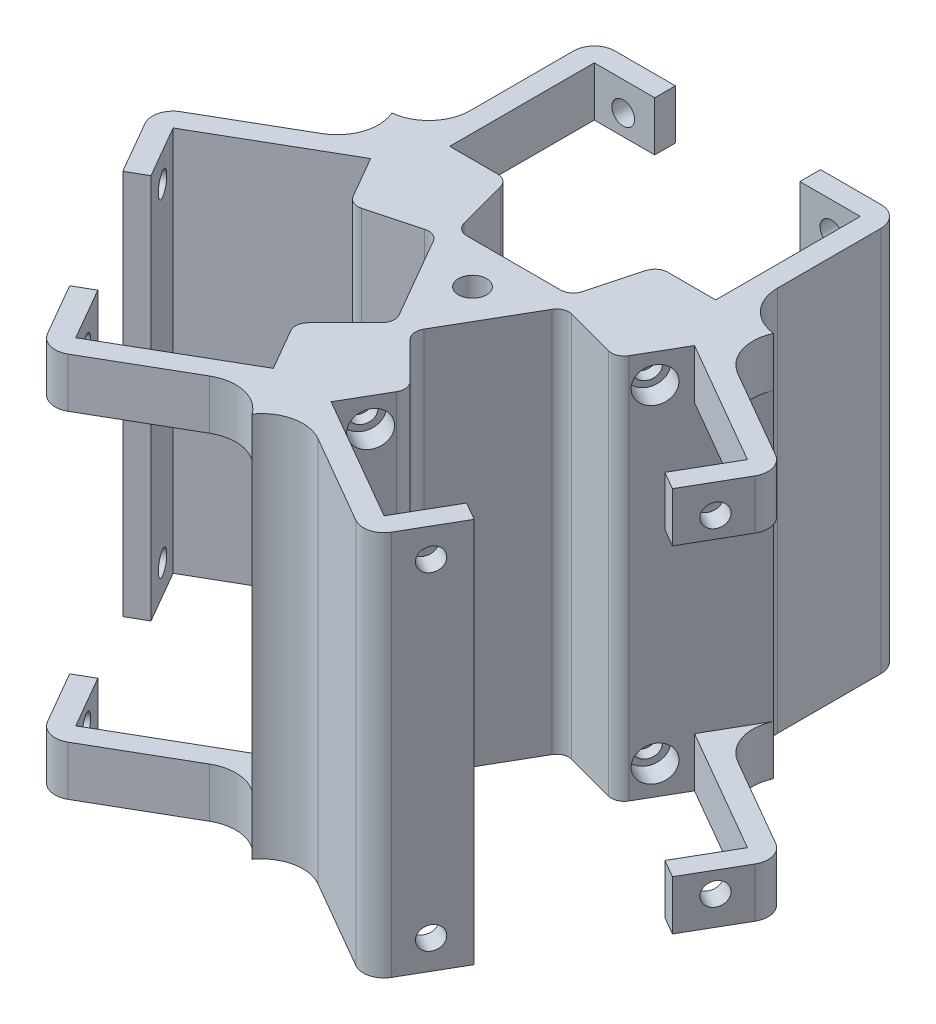
SolidWorks part; units mm, degrees
material "ABS"
ref_plane "Alzado" through (0, 0, 0) normal (0, 0, 1) x (1, 0, 0)
ref_plane "Planta" through (0, 0, 0) normal (0, 1, 0) x (1, 0, 0)
ref_plane "Vista lateral" through (0, 0, 0) normal (1, 0, 0) x (0, 0, -1)
sketch "Croquis1" plane through (0, 0, 0) normal (0, 1, 0) x (1, 0, 0)
  line L0 (0, 50.8) -> (0, -50.8) construction
  line L1 (-50.8, 0) -> (50.8, 0) construction
  line L2 (0, 0) -> (-35.921, -35.921) construction
  line L3 (0, 0) -> (35.921, -35.921) construction
  line L10 (0, -17.5) -> (-15.1554, 8.75) construction
  line L11 (-15.1554, 8.75) -> (15.1554, 8.75) construction
  line L12 (15.1554, 8.75) -> (0, -17.5) construction
  line L13 (-1.2978, -16.7522) -> (-15.1813, 7.2027) construction
  line L14 (1.2978, -16.7522) -> (15.1813, 7.2027) construction
  line L15 (-13.8835, 9.4549) -> (13.8835, 9.4549) construction
  line L16 (1.6964, -16.0645) -> (13.335, -27.7031)
  line L17 (13.335, -27.7031) -> (0, -50.8)
  line L18 (0, -50.8) -> (-13.335, -27.7031)
  line L19 (-13.335, -27.7031) -> (-1.6964, -16.0645)
  line L20 (-17.3241, 25.4) -> (-13.0641, 9.5013)
  line L21 (-43.9941, 25.4) -> (-17.3241, 25.4)
  line L22 (-30.6591, 2.3031) -> (-43.9941, 25.4)
  line L23 (-14.7604, 6.5631) -> (-30.6591, 2.3031)
  line L24 (30.6591, 2.3031) -> (14.7604, 6.5631)
  line L25 (43.9941, 25.4) -> (30.6591, 2.3031)
  line L26 (17.3241, 25.4) -> (43.9941, 25.4)
  line L27 (13.0641, 9.5013) -> (17.3241, 25.4)
  line L28 (-14.7604, 6.5631) -> (-1.6964, -16.0645)
  line L29 (1.6964, -16.0645) -> (14.7604, 6.5631)
  line L30 (-13.0641, 9.5013) -> (13.0641, 9.5013)
  line L31 (-43.9941, 25.4) -> (0, -50.8) construction
  line L32 (43.9941, 25.4) -> (0, -50.8) construction
  line L33 (-43.9941, 25.4) -> (43.9941, 25.4) construction
  circle A0 centre (0, 0) radius 50.8 construction
  circle A7 centre (0, 0) radius 17.5 construction
  circle A8 centre (-13.8835, 7.9549) radius 1.5 construction
  circle A9 centre (13.8835, 7.9549) radius 1.5 construction
  circle A10 centre (0, -16) radius 1.5 construction
  arc A11 (-15.1813, 7.2027) -> (-13.8835, 9.4549) centre (-13.8835, 7.9549) cw construction
  arc A12 (15.1813, 7.2027) -> (13.8835, 9.4549) centre (13.8835, 7.9549) ccw construction
  arc A13 (1.2978, -16.7522) -> (-1.2978, -16.7522) centre (0, -16) cw construction
  arc A14 (-15.1813, 7.2027) -> (-13.8835, 9.4549) centre (-13.8835, 7.9549) cw construction
  arc A15 (13.8835, 9.4549) -> (15.1813, 7.2027) centre (13.8835, 7.9549) cw construction
  arc A16 (-1.2978, -16.7522) -> (1.2978, -16.7522) centre (0, -16) ccw construction
  circle A17 centre (0, 0) radius 76.2 construction
  point P45 (0, 0)
  dimension "D1" = 101.6
  dimension "D6" = 13.8835
  dimension "D9" = 3
  dimension "D5" = 3
  dimension "D4" = 35
  dimension "D10" = 152.4
  dimension "D2" = 45
  dimension "D3" = 45
  dimension "D7" = 26.67
extrude "Saliente-Extruir1" add sketch "Croquis1" along normal blind 88.9
sketch "Croquis4" plane through (0, 88.9, 0) normal (0, 1, 0) x (1, 0, 0)
  circle A0 centre (0, 0) radius 3.25
  dimension "D1" = 6.5
extrude "Cortar-Extruir1" cut sketch "Croquis4" against normal through all
fillet "Redondeo6" radius 3 5 edges at (-14.7604, 44.45, -6.5631) (1.6964, 44.45, 16.0645) (-1.6964, 44.45, 16.0645) (-13.0641, 44.45, -9.5013) (13.0641, 44.45, -9.5013)
fillet "Redondeo7" radius 3 6 edges at (-17.3241, 44.45, -25.4) (-30.6591, 44.45, -2.3031) (17.3241, 44.45, -25.4) (-13.335, 44.45, 27.7031) (30.6591, 44.45, -2.3031) (13.335, 44.45, 27.7031)
scale "Escala2" scale about centroid uniform scaling yes scale factor 1.05
sketch "Croquis9" plane through (0, 91.1225, 0) normal (0, 1, 0) x (1, 0, 0)
  line L9 (0, 76.2) -> (0, -76.2) construction
  line L10 (76.2, 0) -> (-76.2, 0) construction
  line L41 (-37.1934, 26.6702) -> (-37.1934, 61.6702)
  line L42 (-69.5041, -2.9545) -> (-39.1932, 14.5455)
  line L43 (-20.607, 26.6702) -> (-46.1934, 26.6702) construction
  line L44 (-32.1934, 66.6702) -> (-17.5643, 66.6702)
  line L45 (-17.5643, 66.6702) -> (-17.5643, 61.6702)
  line L46 (-17.5643, 61.6702) -> (-32.1934, 61.6702)
  line L47 (-32.1934, 61.6702) -> (-32.1934, 26.6702)
  line L48 (-32.1934, 26.6702) -> (-37.1934, 26.6702)
  line L49 (32.1934, 61.6702) -> (32.1934, 26.6702)
  line L50 (17.5643, 61.6702) -> (32.1934, 61.6702)
  line L51 (17.5643, 66.6702) -> (17.5643, 61.6702)
  line L52 (32.1934, 66.6702) -> (17.5643, 66.6702)
  line L53 (37.1934, 26.6702) -> (37.1934, 61.6702)
  line L54 (32.1934, 26.6702) -> (37.1934, 26.6702)
  line L55 (39.1937, 14.5452) -> (41.6937, 18.8753)
  line L56 (41.6937, 18.8753) -> (72.0046, 1.3753)
  line L57 (73.8347, -5.4548) -> (66.5202, -18.124)
  line L58 (66.5202, -18.124) -> (62.1901, -15.624)
  line L59 (62.1901, -15.624) -> (69.5046, -2.9548)
  line L60 (69.5046, -2.9548) -> (39.1937, 14.5452)
  line L61 (37.3112, -58.7154) -> (7.0003, -41.2154)
  line L62 (7.0003, -41.2154) -> (4.5003, -45.5455)
  line L63 (4.5003, -45.5455) -> (34.8112, -63.0455)
  line L64 (41.6414, -61.2154) -> (48.9559, -48.5462)
  line L65 (48.9559, -48.5462) -> (44.6258, -46.0462)
  line L66 (44.6258, -46.0462) -> (37.3112, -58.7154)
  line L79 (-39.1937, 14.5452) -> (-41.6937, 18.8753) [skipped]
  line L80 (-39.1932, 14.5455) -> (-41.6932, 18.8756)
  line L81 (-41.6937, 18.8753) -> (-72.0046, 1.3753) [skipped]
  line L83 (-41.6932, 18.8756) -> (-72.0041, 1.3756)
  line L85 (-69.5046, -2.9548) -> (-39.1937, 14.5452) [skipped]
  line L86 (-62.1901, -15.624) -> (-69.5046, -2.9548) [skipped]
  line L87 (-66.5202, -18.124) -> (-62.1901, -15.624) [skipped]
  line L88 (-73.8347, -5.4548) -> (-66.5202, -18.124) [skipped]
  line L89 (-73.8342, -5.4545) -> (-66.5197, -18.1237)
  line L90 (-66.5197, -18.1237) -> (-62.1896, -15.6237)
  line L91 (-62.1896, -15.6237) -> (-69.5041, -2.9545)
  line L92 (-46.1934, 26.6702) -> (-33.4002, 4.5117) construction
  line L93 (-7.0003, -41.2154) -> (-4.5003, -45.5455) [skipped]
  line L94 (-4.5003, -45.5455) -> (-34.8112, -63.0455) [skipped]
  line L95 (-41.6414, -61.2154) -> (-48.9559, -48.5462) [skipped]
  line L96 (-48.9559, -48.5462) -> (-44.6258, -46.0462) [skipped]
  line L97 (-44.6258, -46.0462) -> (-37.3112, -58.7154) [skipped]
  line L98 (-37.3112, -58.7154) -> (-7.0003, -41.2154) [skipped]
  line L99 (-6.9998, -41.2151) -> (-4.4998, -45.5452)
  line L100 (-4.4998, -45.5452) -> (-34.8107, -63.0452)
  line L101 (-41.6408, -61.2151) -> (-48.9554, -48.5459)
  line L102 (-48.9554, -48.5459) -> (-44.6253, -46.0459)
  line L103 (-44.6253, -46.0459) -> (-37.3107, -58.7151)
  line L104 (-37.3107, -58.7151) -> (-6.9998, -41.2151)
  line L105 (-12.7928, -31.1813) -> (0.0004, -53.3398) construction
  circle A0 centre (0, 0) radius 101.6 construction
  circle A1 centre (0, 0) radius 76.2 construction
  arc A8 (-37.1934, 61.6702) -> (-32.1934, 66.6702) centre (-32.1934, 61.6702) cw
  arc A9 (37.1934, 61.6702) -> (32.1934, 66.6702) centre (32.1934, 61.6702) ccw
  arc A10 (72.0046, 1.3753) -> (73.8347, -5.4548) centre (69.5046, -2.9548) cw
  arc A11 (34.8112, -63.0455) -> (41.6414, -61.2154) centre (37.3112, -58.7154) ccw
  arc A14 (-72.0046, 1.3753) -> (-73.8347, -5.4548) centre (-69.5046, -2.9548) ccw [skipped]
  arc A15 (-72.0041, 1.3756) -> (-73.8342, -5.4545) centre (-69.5041, -2.9545) ccw
  arc A16 (-34.8112, -63.0455) -> (-41.6414, -61.2154) centre (-37.3112, -58.7154) cw [skipped]
  arc A17 (-34.8107, -63.0452) -> (-41.6408, -61.2151) centre (-37.3107, -58.7151) cw
  point P55 (0.0002, 0.0003)
  point P56 (-1.3626, -0.7865)
  point P58 (0, 0)
  point P61 (0.0002, 0.0003)
  dimension "D1" = 152.4
  dimension "D2" = 203.2
  dimension "D3" = 5
  dimension "D9" = 2
  dimension "D4" = 9
  dimension "D5" = 35
  dimension "D6" = 3
  dimension "D7" = 2
sketch "Croquis12" plane through (0, 91.1225, 0) normal (0, 1, 0) x (1, 0, 0)
  circle A0 centre (0, 0) radius 76.2 construction
  circle A1 centre (0, 0) radius 101.6 construction
  dimension "D1" = 152.4
  dimension "D2" = 203.2
extrude "Saliente-Extruir2" add sketch "Croquis9" against normal through all
sketch "Croquis14" plane through (0, 0, -66.6702) normal (0, 0, -1) x (-1, 0, 0)
  line L0 (-32.1934, -2.2225) -> (-32.1934, 91.1225) construction
  line L1 (17.5643, 91.1225) -> (32.1934, 91.1225) construction
  circle A0 centre (25.1934, 84.1225) radius 2.75
  circle A1 centre (25.1934, 4.7775) radius 2.75
  circle A2 centre (-25.1934, 4.7775) radius 2.75
  circle A3 centre (-25.1934, 84.1225) radius 2.75
  dimension "D1" = 5.5
  dimension "D2" = 7
  dimension "D3" = 7
  dimension "D4" = 7
  dimension "D5" = 7
  dimension "D6" = 7
  dimension "D7" = 7
extrude "Cortar-Extruir2" cut sketch "Croquis14" against normal blind 10
sketch "Croquis15" plane through (0, 0, -26.6702) normal (0, 0, -1) x (-1, 0, 0)
  line L0 (32.1934, -2.2225) -> (32.1934, 91.1225) construction
  line L1 (-32.1934, -2.2225) -> (-20.6078, -2.2225) construction
  line L2 (-32.1934, 91.1225) -> (-20.6078, 91.1225) construction
  circle A0 centre (-25.1934, 4.7775) radius 4.25
  circle A1 centre (25.1934, 4.7775) radius 4.25
  circle A2 centre (-25.1934, 84.1225) radius 4.25
  circle A3 centre (25.1934, 84.1225) radius 4.25
  dimension "D1" = 8.5
  dimension "D2" = 7
  dimension "D3" = 7
  dimension "D4" = 7
  dimension "D5" = 7
  dimension "D6" = 7
  dimension "D7" = 7
extrude "Cortar-Extruir3" cut sketch "Croquis15" against normal blind 5.5
sketch "Croquis16" plane through (0, 0, -21.1702) normal (0, 0, -1) x (-1, 0, 0)
  circle A0 centre (-25.1934, 4.7775) radius 2.775
  circle A1 centre (25.1934, 4.7775) radius 2.775
  circle A2 centre (25.1934, 84.1225) radius 2.775
  circle A3 centre (-25.1934, 84.1225) radius 2.775
  dimension "D1" = 5.55
extrude "Cortar-Extruir4" cut sketch "Croquis16" against normal blind 3
pattern_circular "MatrizC7" count 3 over 360 about axis through (0.0004, -2.2225, -0.0002) along (0, 1, 0) of "Cortar-Extruir4", "Cortar-Extruir3"
sketch "Croquis17" plane through (18.5967, 0, -32.2104) normal (0.5, 0, -0.866) x (-0.866, 0, -0.5)
  line L0 (-26.6703, 91.1225) -> (-26.6703, -2.2225) construction
  line L1 (-26.6703, 79.1225) -> (-68.6703, 79.1225)
  line L2 (-26.6703, 79.1225) -> (-26.6703, 9.7775)
  line L3 (-26.6703, 9.7775) -> (-68.6703, 9.7775)
  line L4 (-68.6703, 79.1225) -> (-68.6703, 9.7775)
  line L5 (76.2, 91.1225) -> (-76.2, 91.1225) construction
  line L6 (-61.6702, -2.2225) -> (-26.6703, -2.2225) construction
  dimension "D1" = 42
  dimension "D2" = 12
  dimension "D3" = 12
extrude "Cortar-Extruir5" cut sketch "Croquis17" against normal blind 31
sketch "Croquis18" plane through (-37.1934, 0, 0) normal (-1, 0, 0) x (0, 0, 1)
  line L0 (-26.6702, 91.1225) -> (-26.6702, -2.2225) construction
  line L1 (-26.6702, 79.1225) -> (-71.6702, 79.1225)
  line L2 (-26.6702, 79.1225) -> (-26.6702, 9.7775)
  line L3 (-26.6702, 9.7775) -> (-71.6702, 9.7775)
  line L4 (-71.6702, 79.1225) -> (-71.6702, 9.7775)
  line L5 (101.6, 91.1225) -> (-101.6, 91.1225) construction
  line L6 (-61.6702, -2.2225) -> (-26.6702, -2.2225) construction
  dimension "D1" = 12
  dimension "D2" = 12
  dimension "D3" = 45
extrude "Cortar-Extruir6" cut sketch "Croquis18" against normal blind 31
fillet "Redondeo8" radius 10 2 edges at (-37.1934, 85.1225, -26.6702) (-37.1934, 3.7775, -26.6702)
fillet "Redondeo9" radius 10 1 edges at (37.1934, 44.45, -26.6702)
fillet "Redondeo12" radius 10 1 edges at (4.5004, 44.45, 45.5456)
fillet "Redondeo13" radius 10 2 edges at (41.6938, 85.1225, -18.8753) (41.6938, 3.7775, -18.8753)
pattern_circular "MatrizC8" count 3 over 360 about axis through (0.0004, 91.1225, -0.0002) along (0, 1, 0) of "Cortar-Extruir6"
fillet "Redondeo14" radius 10 2 edges at (-4.4998, 3.7775, 45.5452) (-4.4998, 85.1225, 45.5452)
fillet "Redondeo16" radius 10 1 edges at (-41.6932, 44.45, -18.8756)
fillet "Redondeo17" radius 3 1 edges at (15.4988, 44.45, -6.8915)
sketch "Croquis20" plane through (-57.7375, 0, 33.3348) normal (-0.866, 0, 0.5) x (0.5, 0, 0.866)
  line L0 (32.1934, -2.2225) -> (32.1934, 9.7775) construction
  line L2 (17.5643, 91.1225) -> (32.1934, 91.1225) construction
  circle A0 centre (25.1934, 4.7775) radius 2.78
  circle A1 centre (25.1934, 84.1225) radius 2.78
  circle A2 centre (-25.1934, 84.1225) radius 2.78
  circle A3 centre (-25.1934, 4.7775) radius 2.78
  point P13 (24.8788, 91.1225)
  dimension "D1" = 5.56
  dimension "D2" = 7
  dimension "D3" = 7
  dimension "D4" = 7
  dimension "D5" = 7
extrude "Cortar-Extruir7" cut sketch "Croquis20" against normal blind 10
sketch "Croquis21" plane through (57.7381, 0, 33.3351) normal (0.866, 0, 0.5) x (0.5, 0, -0.866)
  line L0 (17.5643, 91.1225) -> (32.1934, 91.1225) construction
  line L1 (-32.1934, -2.2225) -> (-32.1934, 91.1225) construction
  line L2 (-32.1934, -2.2225) -> (-17.5643, -2.2225) construction
  circle A0 centre (25.1934, 4.7775) radius 2.775
  circle A1 centre (25.1934, 84.1225) radius 2.775
  circle A2 centre (-25.1934, 84.1225) radius 2.775
  circle A3 centre (-25.1934, 4.7775) radius 2.775
  dimension "D1" = 5.55
  dimension "D2" = 7
  dimension "D3" = 7
  dimension "D4" = 7
  dimension "D5" = 7
extrude "Cortar-Extruir8" cut sketch "Croquis21" against normal blind 10
